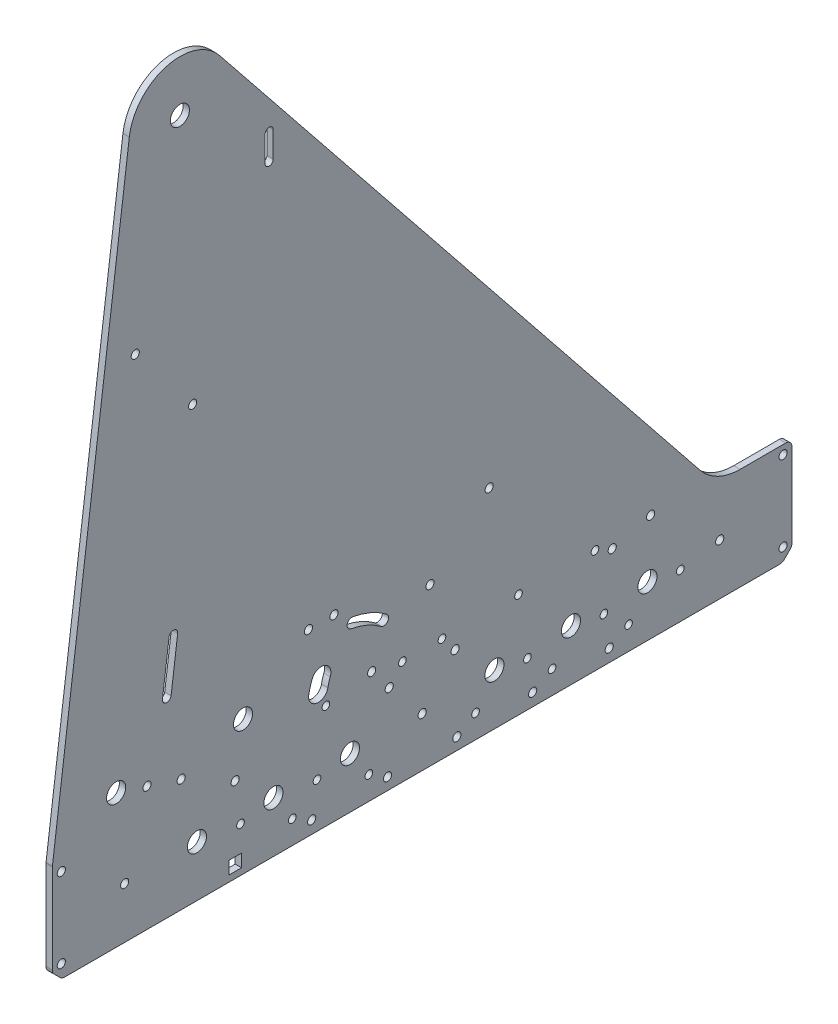
SolidWorks part; units mm, degrees
ref_plane "Front Plane" through (0, 0, 0) normal (0, 0, 1) x (1, 0, 0)
ref_plane "Top Plane" through (0, 0, 0) normal (0, 1, 0) x (1, 0, 0)
ref_plane "Right Plane" through (0, 0, 0) normal (1, 0, 0) x (0, 0, -1)
sketch "Sketch1" plane through (0, 0, 0) normal (1, 0, 0) x (0, 0, -1)
  line L0 (-184.15, -24.6062) -> (184.15, -24.6062)
  line L1 (184.15, -24.6062) -> (184.15, 26.1938)
  line L2 (184.15, 26.1938) -> (146.05, 26.1937)
  line L5 (-145.839, 321.5609) -> (-184.15, 26.1938)
  line L6 (-184.15, 26.1938) -> (-184.15, -24.6062)
  line L7 (-184.15, 350.0437) -> (184.15, 350.0437) construction
  line L9 (146.05, 26.1937) -> (-100.8314, 334.1803)
  arc A0 (-100.8314, 334.1803) -> (-145.839, 321.5609) centre (-120.65, 318.2937) ccw
  point P8 (0, -24.6062)
  dimension "D1" = 368.3
  dimension "D7" = 25.4
  dimension "D2" = 50.8
  dimension "D3" = 38.1
  dimension "D4" = 24.6062
  dimension "D5" = 374.65
  dimension "D6" = 304.8
  dimension "D8" = 342.9
extrude "Boss-Extrude1" add sketch "Sketch1" along normal blind 3.175
chamfer "Chamfer1" distance 4.7625 angle 45 2 edges at (1.5875, -24.6062, 184.15) (1.5875, -24.6062, -184.15)
fillet "Fillet1" radius 25.4 1 edges at (1.5875, 26.1937, -146.05)
fillet "Fillet2" radius 3.175 2 edges at (1.5875, 26.1938, 184.15) (1.5875, 26.1938, -184.15)
fillet "Fillet3" radius 3.175 4 edges at (1.5875, -19.8438, -184.15) (1.5875, -24.6062, -179.3875) (1.5875, -19.8437, 184.15) (1.5875, -24.6062, 179.3875)
sketch "Sketch30" plane through (3.175, 0, 0) normal (1, 0, 0) x (0, 0, -1)
  circle A8 centre (-89.211, 42.2593) radius 4.7625
  circle A9 centre (-25.1593, 30.6938) radius 2.032
  arc A10 (-51.7173, 35.4892) -> (-50.2741, 40.5715) centre (-25.1593, 30.6938) cw construction
  arc A11 (-54.7652, 42.3379) -> (-56.4665, 36.3468) centre (-25.1593, 30.6938) ccw
  arc A12 (-45.783, 38.8051) -> (-46.9681, 34.6317) centre (-25.1593, 30.6938) ccw
  arc A13 (-45.783, 38.8051) -> (-54.7652, 42.3379) centre (-50.2741, 40.5715) ccw
  arc A14 (-56.4665, 36.3468) -> (-46.9681, 34.6317) centre (-51.7173, 35.4892) ccw
  arc A15 (-34.9881, 56.6661) -> (-19.1131, 49.8125) centre (-41.7582, 19.1724) cw construction
  arc A16 (-17.6789, 51.753) -> (-34.5594, 59.0407) centre (-41.7582, 19.1724) ccw
  arc A17 (-20.5473, 47.8719) -> (-35.4169, 54.2915) centre (-41.7582, 19.1724) ccw
  arc A18 (-20.5473, 47.8719) -> (-17.6789, 51.753) centre (-19.1131, 49.8125) ccw
  arc A19 (-34.5594, 59.0407) -> (-35.4169, 54.2915) centre (-34.9881, 56.6661) ccw
  arc A20 (-19.1131, 49.8125) -> (-34.9881, 56.6661) centre (-41.7582, 19.1724) ccw construction
  circle A21 centre (94.6345, 23.8125) radius 2.032
  circle A22 centre (-56.6241, 64.5541) radius 2.032
  circle A23 centre (-43.9241, 64.5541) radius 2.032
  circle A24 centre (-56.6241, 64.5541) radius 1.905 construction
  circle A25 centre (-43.9241, 64.5541) radius 1.905 construction
  point P7 (-51.1204, 38.0658)
  point P19 (-26.6567, 54.1518)
  dimension "D2" = 9.652
  dimension "D4" = 4.064
  dimension "D1" = 4.064
  dimension ".375" = 9.525
  dimension "D3" = 4.826
extrude "Cut-Extrude9" cut sketch "Sketch30" against normal through all
sketch "Sketch16" plane through (3.175, 0, 0) normal (1, 0, 0) x (0, 0, -1)
  circle A0 centre (112.1746, 0.7937) radius 4.7625
  circle A1 centre (74.0746, 0.7937) radius 4.7625
  circle A2 centre (35.9746, 0.7937) radius 4.7625
  circle A3 centre (-35.9746, 0.7938) radius 4.7625
  circle A4 centre (-74.0746, 0.7938) radius 4.7625
  circle A5 centre (-112.1746, 0.7937) radius 4.7625
  dimension "D1" = 9.525
  dimension "D2" = 9.525
extrude "Cut-Extrude1" cut sketch "Sketch16" against normal up to next
sketch "Sketch25" plane through (3.175, 0, 0) normal (1, 0, 0) x (0, 0, -1)
  circle A0 centre (102.7672, -13.0003) radius 1.905 construction
  circle A1 centre (86.0486, 27.3622) radius 1.905 construction
  circle A2 centre (128.5804, -2.3081) radius 1.905 construction
  circle A3 centre (102.7672, -13.0003) radius 1.905
  circle A4 centre (86.0486, 27.3622) radius 1.905
  circle A5 centre (128.5804, -2.3081) radius 1.905
  circle A6 centre (64.6672, -13.0003) radius 1.905 construction
  circle A8 centre (-9.8486, 27.3622) radius 1.905 construction
  circle A10 centre (-47.9486, 27.3622) radius 1.905 construction
  circle A11 centre (-90.4804, -2.3081) radius 1.905 construction
  circle A12 centre (-64.6672, -13.0003) radius 1.905 construction
  circle A14 centre (-52.3804, -2.3081) radius 1.905 construction
  circle A15 centre (-26.5672, -13.0003) radius 1.905 construction
  circle A16 centre (9.8486, 27.3622) radius 1.905 construction
  circle A17 centre (26.5672, -13.0003) radius 1.905 construction
  circle A18 centre (47.9486, 27.3622) radius 1.905 construction
  circle A19 centre (52.3804, -2.3081) radius 1.905 construction
  circle A20 centre (90.4804, -2.3081) radius 1.905 construction
  circle A21 centre (-9.8486, 27.3622) radius 1.905
  circle A23 centre (-47.9486, 27.3622) radius 1.905
  circle A24 centre (-90.4804, -2.3081) radius 1.905
  circle A25 centre (-64.6672, -13.0003) radius 1.905
  circle A27 centre (-52.3804, -2.3081) radius 1.905
  circle A28 centre (-26.5672, -13.0003) radius 1.905
  circle A29 centre (9.8486, 27.3622) radius 1.905
  circle A30 centre (26.5672, -13.0003) radius 1.905
  circle A31 centre (47.9486, 27.3622) radius 1.905
  circle A32 centre (64.6672, -13.0003) radius 1.905
  circle A33 centre (52.3804, -2.3081) radius 1.905
  circle A34 centre (90.4804, -2.3081) radius 1.905
extrude "Cut-Extrude4" cut sketch "Sketch25" against normal up to next
sketch "Sketch23" plane through (3.175, 0, 0) normal (1, 0, 0) x (0, 0, -1)
  circle A0 centre (179.705, 21.7488) radius 1.905 construction
  point P0 (-55.0246, -18.3223)
  point P6 (-93.1246, 17.5943)
  point P9 (-17.2515, -18.6426)
  point P12 (-16.4124, 19.3854)
  point P15 (16.4124, 19.3854)
  point P18 (17.2515, -18.6426)
  point P21 (55.0246, -18.3223)
  point P35 (3.8736, 53.6853)
  point P38 (113.7728, 28.6594)
  point P41 (-137.0088, 37.226)
  point P44 (-179.705, 21.7487)
  point P47 (-179.705, -18.0026)
  point P50 (179.705, 21.7488)
  point P53 (179.705, -18.0026)
  point P59 (93.1246, -18.3223)
hole_wizard "#8 (0.16) Diameter Hole1" positions "Sketch23" profile "Sketch24" hole size "#8" standard "ANSI Inch" end condition up to next
sketch "Sketch24" plane through (3.175, -18.3223, 55.0246) normal (0, 1, 0) x (0, 0, -1)
  line L0 (0, 0) -> (0, 3.175)
  line L1 (0, 3.175) -> (2.032, 3.175)
  line L2 (2.032, 3.175) -> (2.032, 0)
  line L5 (2.032, 0) -> (0, 0)
  line L11 (0, -6.35) -> (0, 107.95) construction
  dimension "Thru Hole Dia." = 4.064
  dimension "Thru Hole Depth" = 3.175
sketch "Sketch22" plane through (3.175, 0, 0) normal (1, 0, 0) x (0, 0, -1)
  line L0 (-96.2996, -15.1473) -> (-89.9496, -15.1473) construction
  line L1 (-96.2996, -15.1473) -> (-89.9496, -15.1473)
  line L2 (-96.2996, -15.1473) -> (-96.2996, -21.4973)
  line L3 (-96.2996, -21.4973) -> (-89.9496, -21.4973)
  line L4 (-89.9496, -15.1473) -> (-89.9496, -21.4973)
  line L5 (-96.2996, -15.1473) -> (-89.9496, -21.4973) construction
  line L6 (-96.2996, -21.4973) -> (-89.9496, -15.1473) construction
  line L7 (-89.9496, -15.1473) -> (-89.9496, -19.8734) construction
  point P0 (-93.1246, -18.3223)
  dimension "D1" = 6.35
extrude "Cut-Extrude3" cut sketch "Sketch22" against normal up to next
sketch "Sketch21" plane through (3.175, 0, 0) normal (1, 0, 0) x (0, 0, -1)
  circle A0 centre (-148.1579, 0.7937) radius 2.032
  circle A2 centre (0, 0) radius 2.032
  circle A3 centre (148.1579, 0.7938) radius 2.032
  dimension "D1" = 4.064
extrude "Cut-Extrude2" cut sketch "Sketch21" against normal up to next
sketch "Sketch26" [suppressed] plane through (3.175, 0, 0) normal (1, 0, 0) x (0, 0, -1)
  line L0 (-145.839, 321.5609) -> (-184.1236, 26.3971) construction
  line L1 (-178.0724, -24.6062) -> (178.0724, -24.6062) construction
  circle A0 centre (-121.0218, 216.6937) radius 15.24
  dimension "D1" = 30.48
  dimension "D2" = 38.1
  dimension "D3" = 241.3
extrude "Cut-Extrude5" [suppressed] cut sketch "Sketch26" against normal through all
sketch "Sketch27" plane through (3.175, 0, 0) normal (1, 0, 0) x (0, 0, -1)
  circle A0 centre (-120.65, 318.2937) radius 4.7625
  dimension "D1" = 9.525
extrude "Cut-Extrude6" cut sketch "Sketch27" against normal through all
sketch "Sketch28" plane through (3.175, 0, 0) normal (1, 0, 0) x (0, 0, -1)
  line L0 (-120.65, 318.2937) -> (-103.5612, 277.2599) construction
  line L1 (-103.5612, 277.2599) -> (-86.3654, 258.566) construction
  line L2 (-86.3654, 258.566) -> (-90.1612, 246.4465) construction
  line L3 (-90.1612, 246.4465) -> (-93.9569, 234.327) construction
  line L4 (-145.839, 321.5609) -> (-184.1236, 26.3971) construction
  circle A0 centre (-93.9569, 234.327) radius 2.032
  circle A1 centre (-90.1612, 246.4465) radius 2.032
  circle A2 centre (-86.3654, 258.566) radius 2.0955
  circle A3 centre (-103.5612, 277.2599) radius 2.032
  dimension "D4" = 4.064
  dimension "D5" = 4.191
  dimension "D6" = 4.064
  dimension "D1" = 25.4
  dimension "D2" = 44.45
  dimension "D3" = 12.7
  dimension "D7" = 30
  dimension "D8" = 120
  dimension "D9" = 160
extrude "Cut-Extrude7" [suppressed] cut sketch "Sketch28" against normal through all
sketch "Sketch29" plane through (3.175, 0, 0) normal (1, 0, 0) x (0, 0, -1)
  line L1 (-76.2, 288.925) -> (-76.2, 276.225) construction
  line L2 (-74.168, 288.925) -> (-74.168, 276.225)
  line L3 (-78.232, 288.925) -> (-78.232, 276.225)
  arc A4 (-74.168, 288.925) -> (-78.232, 288.925) centre (-76.2, 288.925) ccw
  arc A5 (-78.232, 276.225) -> (-74.168, 276.225) centre (-76.2, 276.225) ccw
  point P8 (-76.2, 282.575)
  dimension "D1" = 276.225
  dimension "D2" = 2.032
  dimension "D3" = 76.2
  dimension "D4" = 12.7
sketch "Sketch31" plane through (0, 0, 0) normal (-1, 0, 0) x (0, 0, 1)
  circle A1 centre (114.3, 190.5) radius 2.032
  dimension "D1" = 114.3
  dimension "D6" = 4.064
  dimension "D2" = 190.5
extrude "Cut-Extrude10" cut sketch "Sketch31" against normal through all
sketch "Sketch34" plane through (0, 0, 0) normal (-1, 0, 0) x (0, 0, 1)
  line L3 (123.9045, 95.7355) -> (127.1716, 70.5465) construction
  line L4 (126.0455, 96.0132) -> (129.3127, 70.8242)
  line L5 (121.7634, 95.4578) -> (125.0306, 70.2688)
  line L6 (145.839, 321.5609) -> (184.1236, 26.3971) construction
  arc A2 (126.0455, 96.0132) -> (121.7634, 95.4578) centre (123.9045, 95.7355) ccw
  arc A3 (125.0306, 70.2688) -> (129.3127, 70.8242) centre (127.1716, 70.5465) ccw
  point P9 (125.538, 83.141)
  point P18 (114.3, 190.5)
  dimension "D8" = 4.318
  dimension "D6" = 50.8
  dimension "D7" = 25.4
  dimension "D9" = 95.25
extrude "Cut-Extrude12" cut sketch "Sketch34" against normal through all
sketch "Sketch38" plane through (3.175, 0, 0) normal (1, 0, 0) x (0, 0, -1)
  line L0 (-184.15, 25.9887) -> (-184.15, -18.5286) construction
  line L1 (-178.0724, -24.6062) -> (178.0724, -24.6062) construction
  circle A0 centre (-152.4, 42.0688) radius 4.7625
  dimension "D1" = 31.75
  dimension "D3" = 9.525
  dimension "D2" = 66.675
extrude "Cut-Extrude14" cut sketch "Sketch38" against normal through all
sketch "Sketch37" plane through (3.175, 0, 0) normal (1, 0, 0) x (0, 0, -1)
  circle A0 centre (33.3375, 80.645) radius 2.032
  circle A8 centre (0, 0) radius 2.032 construction
  dimension "D1" = 4.064
  dimension "D2" = 33.3375
  dimension "D3" = 80.645
extrude "Cut-Extrude13" cut sketch "Sketch37" against normal through all
extrude "Cut-Extrude15" cut sketch "Sketch29" against normal through all
sketch "Sketch40" plane through (3.175, 0, 0) normal (1, 0, 0) x (0, 0, -1)
  circle A0 centre (-120.015, 31.75) radius 2.032
  dimension "D1" = 4.064
  dimension "D2" = 120.015
  dimension "D3" = 31.75
extrude "Cut-Extrude16" cut sketch "Sketch40" against normal through all
sketch "Sketch41" [suppressed] plane through (3.175, 0, 0) normal (1, 0, 0) x (0, 0, -1)
  line L0 (-120.65, 318.2937) -> (-98.425, 279.7989) construction
  line L1 (-98.425, 279.7989) -> (-77.6666, 265.1617) construction
  line L2 (-120.65, 318.2937) -> (-60.41, 318.2937) construction
  circle A0 centre (-120.65, 318.2937) radius 25.4 construction
  circle A1 centre (-98.425, 279.7989) radius 19.05 construction
  circle A2 centre (-77.6666, 265.1617) radius 6.35 construction
  circle A3 centre (-98.425, 279.7989) radius 2.032
  circle A4 centre (-77.6666, 265.1617) radius 2.032
  dimension "D1" = 50.8
  dimension "D2" = 38.1
  dimension "D3" = 12.7
  dimension "D4" = 4.064
  dimension "D5" = 60
extrude "Cut-Extrude17" [suppressed] cut sketch "Sketch41" against normal through all
sketch "Sketch43" plane through (3.175, 0, 0) normal (1, 0, 0) x (0, 0, -1)
  line L0 (-152.4, 200.025) -> (-123.6487, 200.025) construction
  line L1 (-115.9779, 252.0412) -> (-152.4, 200.025) construction
  circle A0 centre (-152.4, 200.025) radius 2.032
  arc A1 (-143.2813, 262.8669) -> (-96.4668, 230.087) centre (-152.4, 200.025) cw construction
  arc A2 (-92.2158, 232.3717) -> (-142.5883, 267.6428) centre (-152.4, 200.025) ccw
  arc A3 (-100.7177, 227.8023) -> (-143.9743, 258.0909) centre (-152.4, 200.025) ccw
  arc A4 (-100.7177, 227.8023) -> (-92.2158, 232.3717) centre (-96.4668, 230.087) ccw
  arc A5 (-142.5883, 267.6428) -> (-143.9743, 258.0909) centre (-143.2813, 262.8669) ccw
  point P6 (-115.9779, 252.0412)
  dimension "D1" = 4.064
  dimension "D4" = 4.826
  dimension "D2" = 200.025
  dimension "D3" = 152.4
  dimension "D5" = 63.5
  dimension "D6" = 57.15
  dimension "D7" = 55
extrude "Cut-Extrude19" [suppressed] cut sketch "Sketch43" against normal through all
sketch "Sketch44" plane through (3.175, 0, 0) normal (1, 0, 0) x (0, 0, -1)
  circle A0 centre (-142.875, 226.3775) radius 2.032
  dimension "D1" = 4.064
  dimension "D2" = 142.875
  dimension "D3" = 226.3775
extrude "Cut-Extrude20" cut sketch "Sketch44" against normal through all
sketch "Sketch50" [suppressed] plane through (0, 0, 0) normal (-1, 0, 0) x (0, 0, 1)
  line L0 (90.4875, 206.375) -> (65.0875, 206.375) construction
  line L1 (90.4875, 204.343) -> (65.0875, 204.343)
  line L2 (90.4875, 208.407) -> (65.0875, 208.407)
  line L3 (65.0875, 193.675) -> (39.6875, 193.675) construction
  line L4 (65.0875, 191.643) -> (39.6875, 191.643)
  line L5 (65.0875, 195.707) -> (39.6875, 195.707)
  arc A1 (90.4875, 204.343) -> (90.4875, 208.407) centre (90.4875, 206.375) ccw
  arc A2 (65.0875, 208.407) -> (65.0875, 204.343) centre (65.0875, 206.375) ccw
  arc A3 (65.0875, 191.643) -> (65.0875, 195.707) centre (65.0875, 193.675) ccw
  arc A4 (39.6875, 195.707) -> (39.6875, 191.643) centre (39.6875, 193.675) ccw
  point P3 (77.7875, 206.375)
  point P5 (52.3875, 193.675)
  dimension "D1" = 2.032
  dimension "D2" = 90.4875
  dimension "D3" = 206.375
  dimension "D4" = 25.4
  dimension "D5" = 12.7
extrude "Cut-Extrude22" [suppressed] cut sketch "Sketch50" against normal through all
sketch "Sketch51" [suppressed] plane through (3.175, 0, 0) normal (1, 0, 0) x (0, 0, -1)
  circle A0 centre (-111.125, 222.6469) radius 2.032
  circle A1 centre (-111.125, 190.8969) radius 2.032
  dimension "D1" = 222.6469
  dimension "D3" = 31.75
  dimension "D4" = 4.064
  dimension "D2" = 111.125
extrude "Cut-Extrude23" [suppressed] cut sketch "Sketch51" against normal through all
sketch "Sketch52" [suppressed] plane through (0, 0, 0) normal (-1, 0, 0) x (0, 0, 1)
  line L0 (145.839, 321.5609) -> (184.1236, 26.3971) construction
  line L1 (142.875, 226.3775) -> (142.0856, 251.7652) construction
  line L2 (120.4939, 238.3877) -> (142.875, 226.3775) construction
  arc A5 (142.0856, 251.7652) -> (120.4939, 238.3877) centre (142.875, 226.3775) ccw construction
  arc A6 (142.0224, 253.7962) -> (118.7034, 239.3485) centre (142.875, 226.3775) ccw
  arc A7 (142.1487, 249.7342) -> (122.2844, 237.4269) centre (142.875, 226.3775) ccw
  arc A8 (142.1487, 249.7342) -> (142.0224, 253.7962) centre (142.0856, 251.7652) ccw
  arc A9 (118.7034, 239.3485) -> (122.2844, 237.4269) centre (120.4939, 238.3877) ccw
  point P4 (129.4975, 247.9692)
  dimension "D1" = 25.4
  dimension "D2" = 2.032
  dimension "D3" = 12.7
  dimension "D4" = 60
extrude "Cut-Extrude24" [suppressed] cut sketch "Sketch52" against normal through all
sketch "Sketch53" [suppressed] plane through (3.175, 0, 0) normal (1, 0, 0) x (0, 0, -1)
  line L0 (-35.2284, 197.2663) -> (-35.2284, 135.876) construction
  line L1 (-33.1964, 197.2663) -> (-33.1964, 135.876)
  line L2 (-37.2604, 197.2663) -> (-37.2604, 135.876)
  arc A0 (-33.1964, 197.2663) -> (-37.2604, 197.2663) centre (-35.2284, 197.2663) ccw
  arc A1 (-37.2604, 135.876) -> (-33.1964, 135.876) centre (-35.2284, 135.876) ccw
  point P2 (-35.2284, 166.5712)
  dimension "D1" = 2.032
  dimension "D2" = 61.3903
  dimension "D3" = 197.2663
  dimension "D4" = 35.2284
extrude "Cut-Extrude25" [suppressed] cut sketch "Sketch53" against normal through all
